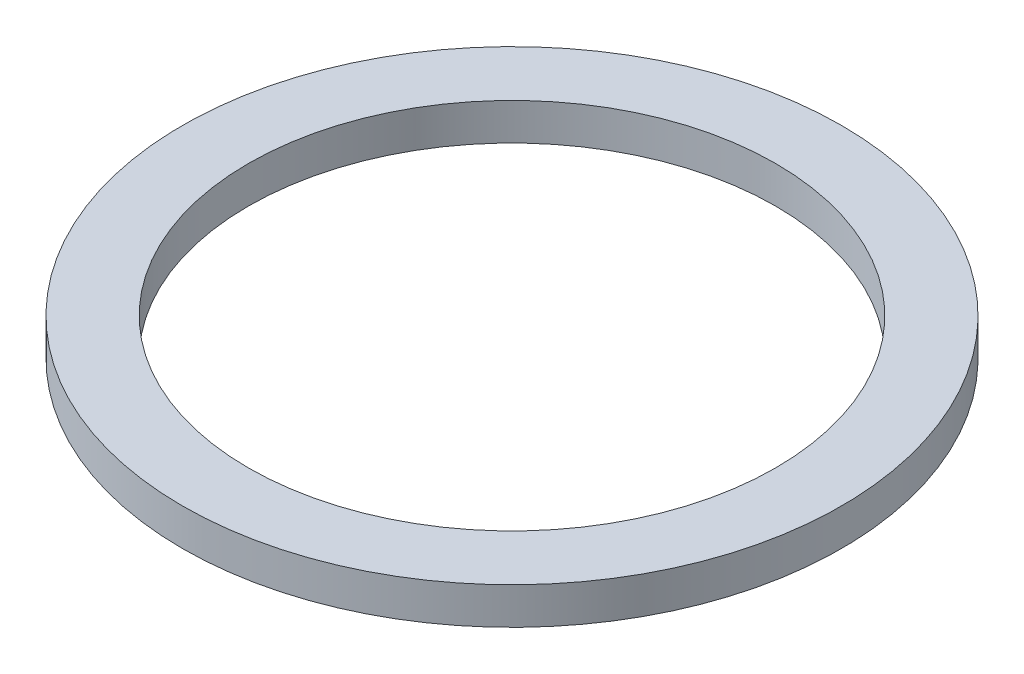
SolidWorks part; units mm, degrees
ref_plane "Front Plane" through (0, 0, 0) normal (0, 0, 1) x (1, 0, 0)
ref_plane "Top Plane" through (0, 0, 0) normal (0, 1, 0) x (1, 0, 0)
ref_plane "Right Plane" through (0, 0, 0) normal (1, 0, 0) x (0, 0, -1)
sketch "Sketch1" plane through (0, 0, 0) normal (0, 1, 0) x (1, 0, 0)
  circle A0 centre (0, 0) radius 62.5
  dimension "FLANGE_OD" = 125
extrude "Boss-Extrude1" add sketch "Sketch1" along normal blind 7
sketch "Sketch2" plane through (0, 0, 0) normal (0, 1, 0) x (1, 0, 0)
  circle A0 centre (0, 0) radius 50
  dimension "BORE_D" = 100
extrude "Cut-Extrude1" cut sketch "Sketch2" along normal through all
sketch "Sketch3" plane through (0, 7, 0) normal (0, 1, 0) x (1, 0, 0)
  circle A0 centre (0, 0) radius 28.628 construction
  circle A1 centre (-28.628, 0) radius 2.0182
  dimension "BOLT_D" = 4.0363
  dimension "BOLT_PCD" = 57.2559
extrude "Cut-Extrude2" cut sketch "Sketch3" against normal blind 6.4988 rebuild error yes
pattern_circular "CirPattern1" count 8 over 360 rebuild error yes
